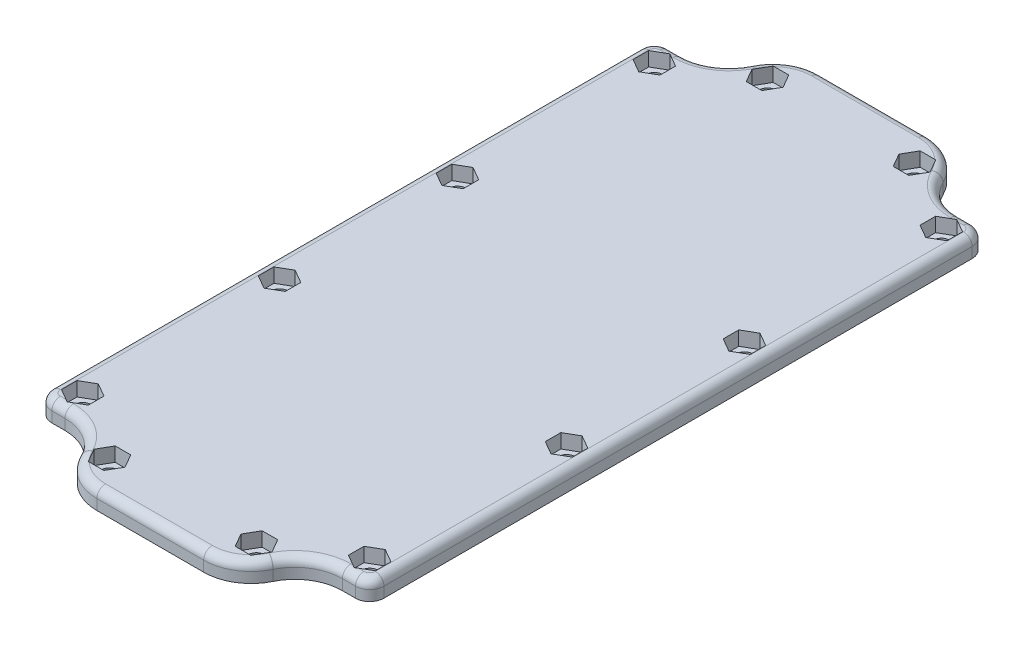
SolidWorks part; units mm, degrees
ref_plane "Спереди" through (0, 0, 0) normal (0, 0, 1) x (1, 0, 0)
ref_plane "Сверху" through (0, 0, 0) normal (0, 1, 0) x (1, 0, 0)
ref_plane "Справа" through (0, 0, 0) normal (1, 0, 0) x (0, 0, -1)
sketch "Эскиз1" plane through (0, 0, 0) normal (0, 1, 0) x (1, 0, 0)
  line L0 (-29.2421, -65) -> (-32, -65)
  line L1 (-11.2579, -76.2495) -> (11.2579, -76.2495)
  line L2 (32, -65) -> (29.2421, -65)
  line L3 (35, -62) -> (35, 62)
  line L4 (32, 65) -> (29.2421, 65)
  line L5 (-35, -62) -> (-35, 62)
  line L6 (-29.2421, 65) -> (-32, 65)
  line L7 (-11.2579, 76.2495) -> (11.2579, 76.2495)
  line L8 (-20.2583, -70.6078) -> (-20.2417, -70.6418)
  line L9 (20.2583, -70.6078) -> (20.2417, -70.6418)
  line L10 (20.2417, 70.6418) -> (20.2583, 70.6078)
  line L11 (-20.2583, 70.6078) -> (-20.2417, 70.6418)
  arc A0 (-35, -62) -> (-32, -65) centre (-32, -62) ccw
  circle A1 centre (-30.25, -60.25) radius 1.75
  arc A2 (-20.2583, -70.6078) -> (-29.2421, -65) centre (-29.2421, -75) ccw
  circle A3 centre (-15.4902, -69.356) radius 1.75
  arc A4 (-20.2417, -70.6418) -> (-11.2579, -76.2495) centre (-11.2579, -66.2495) ccw
  circle A5 centre (15.4902, -69.356) radius 1.75
  arc A6 (11.2579, -76.2495) -> (20.2417, -70.6418) centre (11.2579, -66.2495) ccw
  arc A7 (29.2421, -65) -> (20.2583, -70.6078) centre (29.2421, -75) ccw
  arc A8 (32, -65) -> (35, -62) centre (32, -62) ccw
  circle A9 centre (30.25, -60.25) radius 1.75
  circle A10 centre (30.25, -18.75) radius 1.75
  circle A11 centre (-30.25, -18.75) radius 1.75
  circle A12 centre (30.25, 18.75) radius 1.75
  circle A13 centre (-30.25, 18.75) radius 1.75
  arc A14 (35, 62) -> (32, 65) centre (32, 62) ccw
  circle A15 centre (30.25, 60.25) radius 1.75
  arc A16 (20.2583, 70.6078) -> (29.2421, 65) centre (29.2421, 75) ccw
  arc A17 (20.2417, 70.6418) -> (11.2579, 76.2495) centre (11.2579, 66.2495) ccw
  circle A18 centre (15.4902, 69.356) radius 1.75
  arc A19 (-32, 65) -> (-35, 62) centre (-32, 62) ccw
  circle A20 centre (-30.25, 60.25) radius 1.75
  arc A21 (-29.2421, 65) -> (-20.2583, 70.6078) centre (-29.2421, 75) ccw
  circle A22 centre (-15.4902, 69.356) radius 1.75
  arc A23 (-11.2579, 76.2495) -> (-20.2417, 70.6418) centre (-11.2579, 66.2495) ccw
extrude "Бобышка-Вытянуть1" add sketch "Эскиз1" along normal blind 4
sketch "Эскиз2" plane through (0, 4, 0) normal (0, 1, 0) x (1, 0, 0)
  line L0 (0, 76.2495) -> (0, -76.2495) construction
  line L1 (11.2579, 76.2495) -> (-11.2579, 76.2495) construction
  line L2 (-11.2579, -76.2495) -> (11.2579, -76.2495) construction
  line L3 (-35, 0) -> (35, 0) construction
  line L4 (-35, 62) -> (-35, -62) construction
  line L5 (35, -62) -> (35, 62) construction
  line L6 (-33.09, -17.1103) -> (-30.25, -15.4707)
  line L7 (-17.1254, 66.5135) -> (-13.8461, 66.5186)
  line L8 (-13.8461, 66.5186) -> (-12.2108, 69.3612)
  line L9 (-12.2108, 69.3612) -> (-13.855, 72.1986)
  line L10 (-13.855, 72.1986) -> (-17.1343, 72.1935)
  line L11 (-17.1343, 72.1935) -> (-18.7695, 69.3509)
  line L12 (-18.7695, 69.3509) -> (-17.1254, 66.5135)
  line L13 (-30.25, 56.9707) -> (-27.41, 58.6103)
  line L14 (-27.41, 58.6103) -> (-27.41, 61.8897)
  line L15 (-27.41, 61.8897) -> (-30.25, 63.5293)
  line L16 (-30.25, 63.5293) -> (-33.09, 61.8897)
  line L17 (-33.09, 61.8897) -> (-33.09, 58.6103)
  line L18 (-33.09, 58.6103) -> (-30.25, 56.9707)
  line L19 (-30.25, 15.4707) -> (-27.41, 17.1103)
  line L20 (-27.41, 17.1103) -> (-27.41, 20.3897)
  line L21 (-27.41, 20.3897) -> (-30.25, 22.0293)
  line L22 (-30.25, 22.0293) -> (-33.09, 20.3897)
  line L23 (-33.09, 20.3897) -> (-33.09, 17.1103)
  line L24 (-33.09, 17.1103) -> (-30.25, 15.4707)
  line L25 (-33.09, -20.3897) -> (-33.09, -17.1103)
  line L26 (-30.25, -22.0293) -> (-33.09, -20.3897)
  line L27 (-27.41, -20.3897) -> (-30.25, -22.0293)
  line L28 (-27.41, -17.1103) -> (-27.41, -20.3897)
  line L29 (-30.25, -15.4707) -> (-27.41, -17.1103)
  line L30 (-33.09, -58.6103) -> (-30.25, -56.9707)
  line L31 (-33.09, -61.8897) -> (-33.09, -58.6103)
  line L32 (-30.25, -63.5293) -> (-33.09, -61.8897)
  line L33 (-27.41, -61.8897) -> (-30.25, -63.5293)
  line L34 (-27.41, -58.6103) -> (-27.41, -61.8897)
  line L35 (-30.25, -56.9707) -> (-27.41, -58.6103)
  line L36 (-18.7695, -69.3509) -> (-17.1254, -66.5135)
  line L37 (-17.1343, -72.1935) -> (-18.7695, -69.3509)
  line L38 (-13.855, -72.1986) -> (-17.1343, -72.1935)
  line L39 (-12.2108, -69.3612) -> (-13.855, -72.1986)
  line L40 (-13.8461, -66.5186) -> (-12.2108, -69.3612)
  line L41 (-17.1254, -66.5135) -> (-13.8461, -66.5186)
  line L42 (17.1254, -66.5135) -> (13.8461, -66.5186)
  line L43 (13.8461, -66.5186) -> (12.2108, -69.3612)
  line L44 (12.2108, -69.3612) -> (13.855, -72.1986)
  line L45 (13.855, -72.1986) -> (17.1343, -72.1935)
  line L46 (17.1343, -72.1935) -> (18.7695, -69.3509)
  line L47 (18.7695, -69.3509) -> (17.1254, -66.5135)
  line L48 (30.25, -56.9707) -> (27.41, -58.6103)
  line L49 (27.41, -58.6103) -> (27.41, -61.8897)
  line L50 (27.41, -61.8897) -> (30.25, -63.5293)
  line L51 (30.25, -63.5293) -> (33.09, -61.8897)
  line L52 (33.09, -61.8897) -> (33.09, -58.6103)
  line L53 (33.09, -58.6103) -> (30.25, -56.9707)
  line L54 (30.25, -15.4707) -> (27.41, -17.1103)
  line L55 (27.41, -17.1103) -> (27.41, -20.3897)
  line L56 (27.41, -20.3897) -> (30.25, -22.0293)
  line L57 (30.25, -22.0293) -> (33.09, -20.3897)
  line L58 (33.09, -20.3897) -> (33.09, -17.1103)
  line L59 (33.09, 17.1103) -> (30.25, 15.4707)
  line L60 (33.09, 20.3897) -> (33.09, 17.1103)
  line L61 (30.25, 22.0293) -> (33.09, 20.3897)
  line L62 (27.41, 20.3897) -> (30.25, 22.0293)
  line L63 (27.41, 17.1103) -> (27.41, 20.3897)
  line L64 (30.25, 15.4707) -> (27.41, 17.1103)
  line L65 (33.09, 58.6103) -> (30.25, 56.9707)
  line L66 (33.09, 61.8897) -> (33.09, 58.6103)
  line L67 (30.25, 63.5293) -> (33.09, 61.8897)
  line L68 (27.41, 61.8897) -> (30.25, 63.5293)
  line L69 (27.41, 58.6103) -> (27.41, 61.8897)
  line L70 (30.25, 56.9707) -> (27.41, 58.6103)
  line L71 (18.7695, 69.3509) -> (17.1254, 66.5135)
  line L72 (17.1343, 72.1935) -> (18.7695, 69.3509)
  line L73 (13.855, 72.1986) -> (17.1343, 72.1935)
  line L74 (12.2108, 69.3612) -> (13.855, 72.1986)
  line L75 (13.8461, 66.5186) -> (12.2108, 69.3612)
  line L76 (17.1254, 66.5135) -> (13.8461, 66.5186)
  line L77 (33.09, -17.1103) -> (30.25, -15.4707)
  circle A0 centre (-15.4902, 69.356) radius 2.84 construction
  circle A1 centre (-30.25, 60.25) radius 2.84 construction
  circle A2 centre (-30.25, 18.75) radius 2.84 construction
  circle A3 centre (-30.25, -18.75) radius 2.84 construction
  circle A4 centre (-30.25, -60.25) radius 2.84 construction
  circle A5 centre (-15.4902, -69.356) radius 2.84 construction
  circle A6 centre (15.4902, -69.356) radius 2.84 construction
  circle A7 centre (30.25, -60.25) radius 2.84 construction
  circle A8 centre (30.25, -18.75) radius 2.84 construction
  circle A9 centre (30.25, 18.75) radius 2.84 construction
  circle A10 centre (30.25, 60.25) radius 2.84 construction
  circle A11 centre (15.4902, 69.356) radius 2.84 construction
extrude "Вырез-Вытянуть1" cut sketch "Эскиз2" against normal blind 3
fillet "Скругление1" radius 1.8 24 edges at (34.1213, 4, 64.1213) (30.621, 4, 65) (23.9469, 4, 66.517) (20.25, 4, 70.6248) (16.5531, 4, 74.7325) (0, 4, 76.2495) (-16.5531, 4, 74.7325) (-20.25, 4, 70.6248) (-23.9469, 4, 66.517) (-30.621, 4, 65) (-34.1213, 4, 64.1213) (-35, 4, 0) (-34.1213, 4, -64.1213) (-30.621, 4, -65) (-23.9469, 4, -66.517) (-20.25, 4, -70.6248) (-16.5531, 4, -74.7325) (0, 4, -76.2495) (16.5531, 4, -74.7325) (20.25, 4, -70.6248) (23.9469, 4, -66.517) (30.621, 4, -65) (34.1213, 4, -64.1213) (35, 4, 0)
